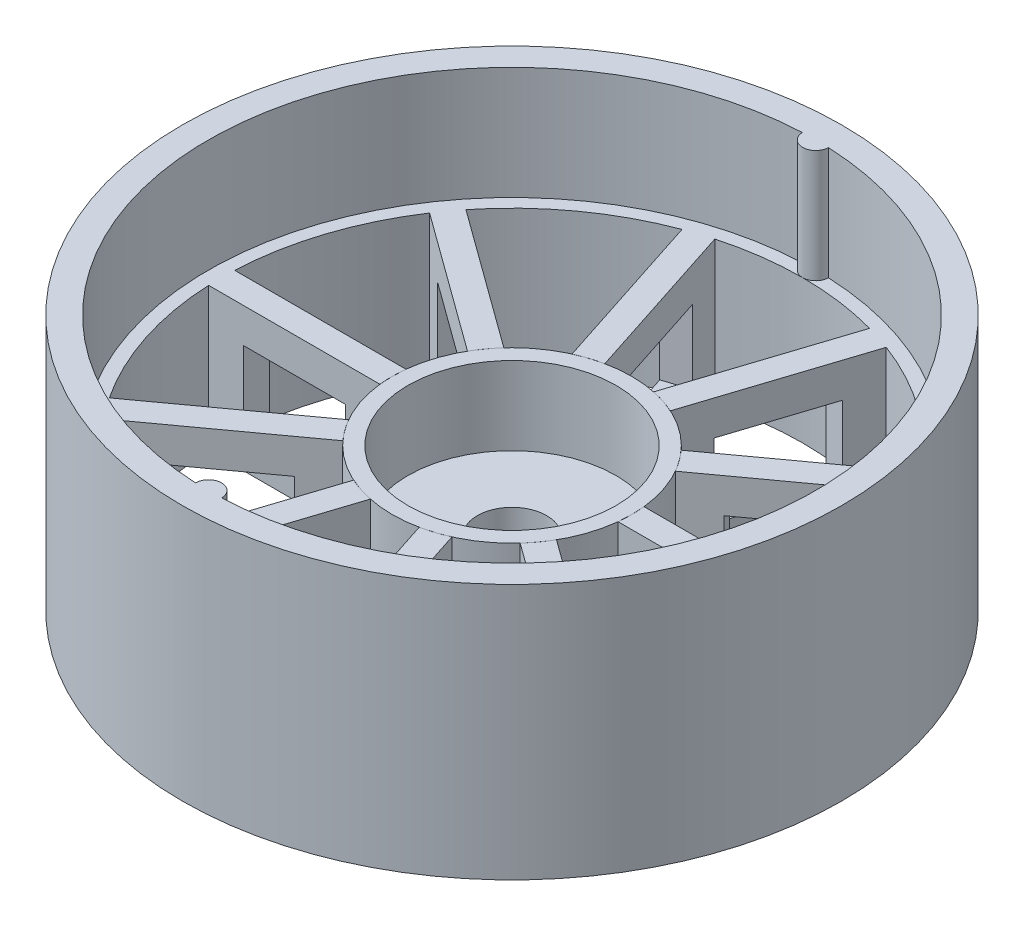
SolidWorks part; units mm, degrees
note: The reader was unsure of these and kept them because the rebuilt part matched: shared geometry of "Sketch1<3>", "Sketch5<3>".
ref_plane "Front Plane" through (0, 0, 0) normal (0, 0, 1) x (1, 0, 0)
ref_plane "Top Plane" through (0, 0, 0) normal (0, 1, 0) x (1, 0, 0)
ref_plane "Right Plane" through (0, 0, 0) normal (1, 0, 0) x (0, 0, -1)
sketch "Sketch1" plane through (0, 0, 0) normal (0, 1, 0) x (1, 0, 0)
  line L3 (0, 35) -> (0, -34.9678) construction
  arc A0 (1.5, -34.9678) -> (1.4997, 34.9679) centre (0, 0) ccw
  circle A1 centre (0, 0) radius 38
  circle A2 centre (0, 0) radius 4
  circle A3 centre (0, 0) radius 35 construction
  arc A7 (-1.4997, 34.9679) -> (1.4997, 34.9679) centre (0, 35) ccw
  arc A9 (-1.4997, 34.9679) -> (-1.5, -34.9679) centre (0, 0) ccw
  arc A11 (1.5, -34.9678) -> (-1.5, -34.9679) centre (0, -34.9678) ccw
  dimension "D1" = 3
  dimension "D2" = 1.5
  dimension "D3" = 4
  dimension "D4" = 35
  dimension "D5" = 1.5
  dimension "D6" = 1.5
  dimension "D7" = 35
  dimension "D11" = 1.4997
extrude "Boss-Extrude1" add sketch "Sketch1" along normal blind 16.5
extrude "Boss-Extrude2" add sketch "Sketch1<3>" along normal blind 29.5
sketch "Sketch1<3>" plane through (0, 0, 0) normal (0, 1, 0) x (1, 0, 0) same geometry as "Sketch1"
sketch "Sketch2" plane through (0, 0, 0) normal (0, -1, 0) x (1, 0, 0)
  line L1 (-3.6373, 6.3) -> (-7.2746, 0)
  line L2 (-7.2746, 0) -> (-3.6373, -6.3)
  line L3 (-3.6373, -6.3) -> (3.6373, -6.3)
  line L4 (3.6373, -6.3) -> (7.2746, 0)
  line L5 (7.2746, 0) -> (3.6373, 6.3)
  line L6 (3.6373, 6.3) -> (-3.6373, 6.3)
  circle A0 centre (0, 0) radius 6.3 construction
  dimension "D2" = 12.6
extrude "Cut-Extrude1" cut sketch "Sketch2" against normal blind 4.5
sketch "Sketch3" plane through (0, 16.5, 0) normal (0, 1, 0) x (1, 0, 0)
  circle A0 centre (0, 0) radius 12
  circle A1 centre (0, 0) radius 4 construction
  dimension "D1" = 24
extrude "Cut-Extrude2" cut sketch "Sketch3" against normal blind 9
sketch "Sketch5" plane through (0, 16.5, 0) normal (0, 1, 0) x (1, 0, 0)
  line L10 (13.8, 0) -> (33.5, 0) construction
  line L11 (13.7182, -1.5) -> (33.4664, -1.5)
  line L12 (13.7182, 1.5) -> (33.4664, 1.5)
  circle A0 centre (0, 0) radius 33.5
  arc A1 (-1.4997, 34.9679) -> (1.4997, 34.9679) centre (0, 35) ccw construction
  circle A2 centre (0, 0) radius 13.8
  circle A3 centre (0, 0) radius 12 construction
  arc M28 (-1.5, -34.9679) -> (1.5, -34.9678) centre (0, -34.9678) cw
  dimension "D1" = 1.8
  dimension "D2" = 3
  dimension "D3" = 1.5
extrude "Cut-Extrude4" cut sketch "Sketch5" against normal through all contours A2 L12 A0 L11 M28 | A2 L10 A0 L12 | L10 A2 L11 A0
sketch "Sketch8" plane through (0, 4.5, 0) normal (0, -1, 0) x (1, 0, 0)
  line L0 (0, 4) -> (4.9652, 4)
  line L1 (7.2746, 0) -> (3.6373, 6.3) construction
  line L2 (0, -4) -> (4.9652, -4)
  line L3 (3.6373, -6.3) -> (7.2746, 0) construction
  line L4 (0, 4) -> (-4.9652, 4)
  line L5 (-3.6373, 6.3) -> (-7.2746, 0) construction
  line L6 (0, -4) -> (-4.9652, -4)
  line L7 (-7.2746, 0) -> (-3.6373, -6.3) construction
  line L8 (-4, 0) -> (-4, 5.6718)
  line L9 (-4, 0) -> (-4, -5.6718)
  line L10 (4, 0) -> (4, 5.6718)
  line L11 (4, 0) -> (4, -5.6718)
  line L12 (3.926, 5.8) -> (-3.926, 5.8)
  line L14 (-3.926, -5.8) -> (3.926, -5.8)
  line L16 (5.8, 2.5541) -> (5.8, -2.5541)
  line L17 (-5.8, -2.5541) -> (-5.8, 2.5541)
  circle A0 centre (0, 0) radius 4 construction
  dimension "D1" = 1.8
  dimension "D2" = 1.8
  dimension "D3" = 1.8
extrude "Boss-Extrude5" [suppressed] add sketch "Sketch8" along normal blind 0.4 separate body
extrude "Boss-Extrude6" add sketch "Sketch5<3>" against normal up to surface (16.5 mm away) contours L10 A2 L11 A0 | A2 L10 A0 L12
sketch "Sketch5<3>" plane through (0, 16.5, 0) normal (0, 1, 0) x (1, 0, 0) same geometry as "Sketch5"
sketch "Sketch6" plane through (-0.8809, 0, -1.5) normal (0, 0, -1) x (-1, 0, 0)
  line L0 (-24.4732, 16.5) -> (-24.4732, 12.5) construction
  line L4 (-24.4732, 0) -> (-24.4732, 4) construction
  line L6 (-34.3473, 8.25) -> (-30.3473, 8.25) construction
  line L8 (-14.5991, 8.25) -> (-18.5991, 8.25) construction
  line L11 (-30.3473, 12.5) -> (-18.5991, 12.5)
  line L12 (-30.3473, 12.5) -> (-30.3473, 4)
  line L13 (-30.3473, 4) -> (-18.5991, 4)
  line L14 (-18.5991, 12.5) -> (-18.5991, 4)
  line L19 (-34.3473, 0) -> (-34.3473, 16.5) construction
  line L20 (-14.5991, 16.5) -> (-34.3473, 16.5) construction
  line L21 (-34.3473, 0) -> (-14.5991, 0) construction
  line L22 (-14.5991, 0) -> (-14.5991, 16.5) construction
  dimension "D1" = 4
  dimension "D2" = 4
extrude "Cut-Extrude5" cut sketch "Sketch6" against normal up to next (3 mm away)
pattern_circular "CirPattern1" count 10 over 360 about axis through (0, 0, 0) along (0, 1, 0) of "Boss-Extrude6", "Cut-Extrude5"
